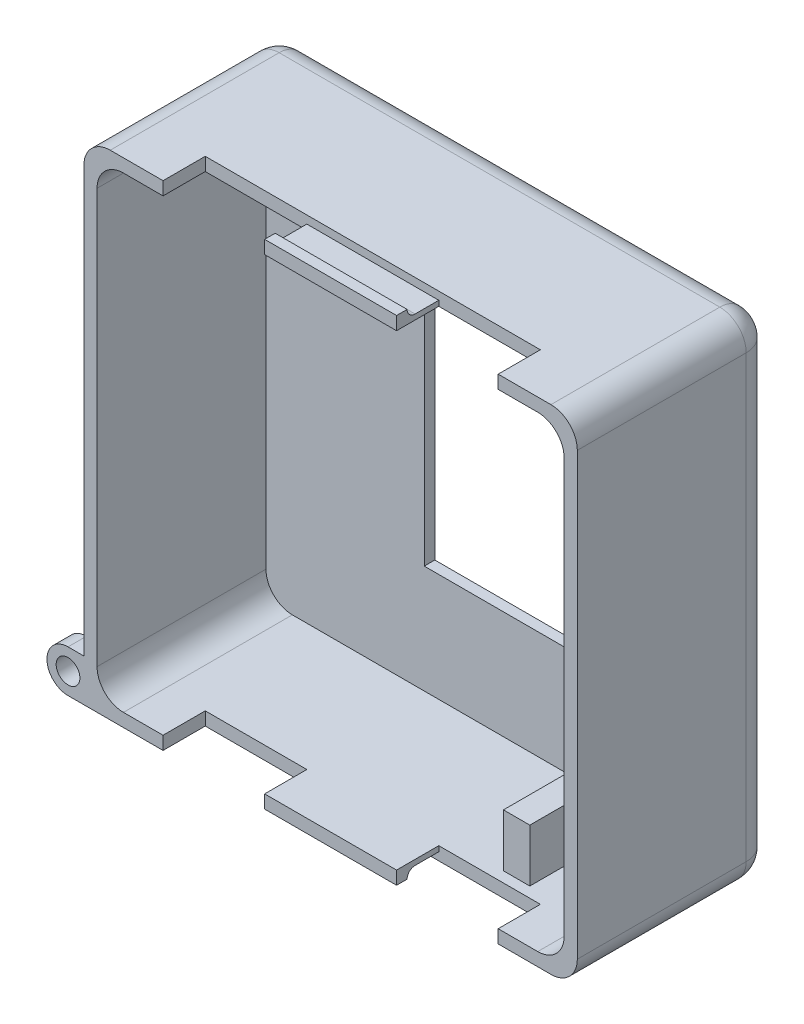
SolidWorks part; units mm, degrees
ref_plane "Front Plane" through (0, 0, 0) normal (0, 0, 1) x (1, 0, 0)
ref_plane "Top Plane" through (0, 0, 0) normal (0, 1, 0) x (1, 0, 0)
ref_plane "Right Plane" through (0, 0, 0) normal (1, 0, 0) x (0, 0, -1)
sketch "Sketch1" plane through (0, 0, 0) normal (0, 0, 1) x (1, 0, 0)
  line L1 (-21.209, -23.749) -> (21.209, -23.749)
  line L2 (-23.749, -21.209) -> (-23.749, 21.209)
  line L3 (-21.209, 23.749) -> (21.209, 23.749)
  line L4 (23.749, -21.209) -> (23.749, 21.209)
  line L5 (-23.749, -23.749) -> (23.749, 23.749) construction
  line L6 (-23.749, 23.749) -> (23.749, -23.749) construction
  arc A0 (-21.209, -23.749) -> (-23.749, -21.209) centre (-21.209, -21.209) cw
  arc A1 (21.209, -23.749) -> (23.749, -21.209) centre (21.209, -21.209) ccw
  arc A2 (21.209, 23.749) -> (23.749, 21.209) centre (21.209, 21.209) cw
  arc A3 (-23.749, 21.209) -> (-21.209, 23.749) centre (-21.209, 21.209) cw
  point P0 (0, 0)
  dimension "D3" = 2.54
  dimension "D1" = 47.498
  dimension "D2" = 47.498
extrude "Boss-Extrude1" add sketch "Sketch1" along normal blind 18.796
sketch "Sketch2" plane through (0, 0, 18.796) normal (0, 0, 1) x (1, 0, 0)
  line L22 (21.209, 23.749) -> (-21.209, 23.749) construction
  line L23 (19.939, -22.479) -> (-19.939, -22.479)
  line L24 (22.479, -19.939) -> (22.479, 19.939)
  line L25 (19.939, 22.479) -> (-19.939, 22.479)
  line L26 (-22.479, -19.939) -> (-22.479, 19.939)
  line L27 (22.479, -22.479) -> (-22.479, 22.479) construction
  line L28 (22.479, 22.479) -> (-22.479, -22.479) construction
  line L29 (-23.749, 21.209) -> (-23.749, -21.209) construction
  arc A14 (-19.939, -22.479) -> (-22.479, -19.939) centre (-19.939, -19.939) cw
  arc A15 (19.939, -22.479) -> (22.479, -19.939) centre (19.939, -19.939) ccw
  arc A16 (22.479, 19.939) -> (19.939, 22.479) centre (19.939, 19.939) ccw
  arc A17 (-19.939, 22.479) -> (-22.479, 19.939) centre (-19.939, 19.939) ccw
  point P12 (0, 0)
  dimension "D3" = 2.54
  dimension "D1" = 1.27
  dimension "D2" = 1.27
extrude "Cut-Extrude1" cut sketch "Sketch2" against normal blind 16.256
fillet "Fillet1" radius 2.54 8 edges at (-23.0051, 23.0051, 0) (0, 23.749, 0) (23.0051, 23.0051, 0) (23.749, 0, 0) (23.0051, -23.0051, 0) (0, -23.749, 0) (-23.0051, -23.0051, 0) (-23.749, 0, 0)
sketch "Sketch3" plane through (0, 23.749, 0) normal (0, 1, 0) x (1, 0, 0)
  line L0 (21.209, -18.796) -> (-21.209, -18.796) construction
  line L1 (16.129, -22.86) -> (-16.129, -22.86)
  line L2 (16.129, -22.86) -> (16.129, -14.732)
  line L3 (16.129, -14.732) -> (-16.129, -14.732)
  line L4 (-16.129, -22.86) -> (-16.129, -14.732)
  line L5 (16.129, -22.86) -> (-16.129, -14.732) construction
  line L6 (16.129, -14.732) -> (-16.129, -22.86) construction
  point P0 (0, -18.796)
  dimension "D1" = 32.258
  dimension "D2" = 4.064
extrude "Cut-Extrude2" cut sketch "Sketch3" against normal through all both and the other way through all
sketch "Sketch5" plane through (0, 0, 0) normal (0, 0, -1) x (-1, 0, 0)
  line L0 (21.209, -21.209) -> (21.209, 21.209) construction
  line L1 (-14.605, 17.145) -> (12.319, 17.145)
  line L2 (-14.605, 17.145) -> (-14.605, -17.145)
  line L3 (-14.605, -17.145) -> (12.319, -17.145)
  line L4 (12.319, 17.145) -> (12.319, -17.145)
  line L5 (-14.605, 17.145) -> (12.319, -17.145) construction
  line L6 (-14.605, -17.145) -> (12.319, 17.145) construction
  point P0 (0, 0)
  dimension "D1" = 26.924
  dimension "D2" = 34.29
  dimension "D3" = 8.89
extrude "Cut-Extrude4" cut sketch "Sketch5" against normal blind 1.524
sketch "Sketch6" plane through (0, 0, 1.524) normal (0, 0, -1) x (-1, 0, 0)
  line L0 (-14.605, 17.145) -> (-14.605, -17.145) construction
  line L1 (-9.525, -12.065) -> (7.239, -12.065)
  line L2 (-9.525, -12.065) -> (-9.525, 12.065)
  line L3 (-9.525, 12.065) -> (7.239, 12.065)
  line L4 (7.239, -12.065) -> (7.239, 12.065)
  line L5 (-9.525, -12.065) -> (7.239, 12.065) construction
  line L6 (-9.525, 12.065) -> (7.239, -12.065) construction
  line L8 (12.319, 17.145) -> (-14.605, 17.145) construction
  line L9 (-14.605, -17.145) -> (12.319, -17.145) construction
  line L10 (12.319, -17.145) -> (12.319, 17.145) construction
  point P0 (0, 0)
  dimension "D1" = 5.08
  dimension "D2" = 5.08
  dimension "D3" = 5.08
  dimension "D4" = 5.08
extrude "Cut-Extrude5" cut sketch "Sketch6" against normal blind 1.524
sketch "Sketch7" plane through (0, 0, 0) normal (0, 0, -1) x (-1, 0, 0)
  line L0 (21.209, 21.209) -> (21.209, -21.209) construction
  line L1 (21.209, 21.209) -> (-21.209, 21.209) construction
  line L2 (-21.209, -21.209) -> (21.209, -21.209) construction
  line L3 (13.589, 21.209) -> (13.589, -21.209) construction
  line L4 (21.209, -21.209) -> (21.209, 21.209) construction
  line L5 (13.589, 17.145) -> (21.209, 17.145) construction
  line L6 (19.939, 17.145) -> (21.209, 17.145)
  line L7 (14.859, 17.145) -> (13.589, 17.145)
  line L8 (21.209, 15.875) -> (16.129, 15.875)
  line L9 (21.209, 10.795) -> (16.129, 10.795)
  line L10 (16.129, 14.605) -> (21.209, 14.605)
  line L11 (21.209, 14.605) -> (21.209, 15.875)
  line L12 (16.129, 12.065) -> (21.209, 12.065)
  line L13 (21.209, 12.065) -> (21.209, 10.795)
  line L14 (13.589, 9.525) -> (21.209, 9.525)
  line L15 (21.209, 9.525) -> (21.209, 5.715)
  line L16 (21.209, 5.715) -> (19.939, 5.715)
  line L17 (19.939, 5.715) -> (19.939, 8.255)
  line L18 (19.939, 8.255) -> (18.034, 8.255)
  line L19 (18.034, 8.255) -> (18.034, 6.985)
  line L20 (18.034, 6.985) -> (16.764, 6.985)
  line L21 (16.764, 6.985) -> (16.764, 8.255)
  line L22 (16.764, 8.255) -> (13.589, 8.255)
  line L23 (13.589, 8.255) -> (13.589, 9.525)
  line L24 (13.589, 4.445) -> (21.209, 4.445)
  line L25 (21.209, 4.445) -> (21.209, 0.635)
  line L26 (21.209, 0.635) -> (19.939, 0.635)
  line L27 (19.939, 0.635) -> (19.939, 3.175)
  line L28 (19.939, 3.175) -> (18.034, 3.175)
  line L29 (18.034, 3.175) -> (18.034, 1.905)
  line L30 (18.034, 1.905) -> (16.764, 1.905)
  line L31 (16.764, 1.905) -> (16.764, 3.175)
  line L32 (16.764, 3.175) -> (13.589, 3.175)
  line L33 (13.589, 3.175) -> (13.589, 4.445)
  line L34 (21.209, -0.635) -> (13.589, -0.635)
  line L35 (13.589, -0.635) -> (13.589, -4.445)
  line L36 (13.589, -4.445) -> (14.859, -4.445)
  line L37 (14.859, -4.445) -> (14.859, -1.905)
  line L38 (14.859, -1.905) -> (21.209, -1.905)
  line L39 (21.209, -1.905) -> (21.209, -0.635)
  line L40 (13.589, -5.715) -> (21.209, -5.715)
  line L41 (21.209, -5.715) -> (21.209, -9.525)
  line L42 (21.209, -9.525) -> (19.939, -9.525)
  line L43 (19.939, -9.525) -> (19.939, -6.985)
  line L44 (19.939, -6.985) -> (18.034, -6.985)
  line L45 (18.034, -6.985) -> (18.034, -8.255)
  line L46 (18.034, -8.255) -> (16.764, -8.255)
  line L47 (16.764, -8.255) -> (16.764, -6.985)
  line L48 (16.764, -6.985) -> (14.859, -6.985)
  line L49 (14.859, -6.985) -> (14.859, -9.525)
  line L50 (14.859, -9.525) -> (13.589, -9.525)
  line L51 (13.589, -9.525) -> (13.589, -5.715)
  line L52 (13.589, -13.0175) -> (21.209, -13.0175) construction
  line L53 (21.209, -13.0175) -> (17.399, -13.0175) construction
  line L54 (17.399, -13.0175) -> (13.589, -13.0175) construction
  line L55 (18.9865, -13.97) -> (18.9865, -15.24)
  line L56 (15.8115, -12.065) -> (15.8115, -10.795)
  line L57 (13.589, -18.7325) -> (21.209, -18.7325) construction
  line L58 (15.8115, -17.78) -> (15.8115, -16.51)
  line L59 (18.9865, -20.955) -> (18.9865, -19.685)
  arc A0 (21.209, 17.145) -> (13.589, 17.145) centre (17.399, 17.145) ccw
  arc A1 (19.939, 17.145) -> (14.859, 17.145) centre (17.399, 17.145) ccw
  arc A2 (16.129, 15.875) -> (16.129, 10.795) centre (16.129, 13.335) ccw
  arc A3 (16.129, 14.605) -> (16.129, 12.065) centre (16.129, 13.335) ccw
  arc A4 (18.9865, -15.24) -> (16.764, -13.0175) centre (18.9865, -13.0175) ccw
  arc A5 (15.8115, -10.795) -> (18.034, -13.0175) centre (15.8115, -13.0175) ccw
  arc A6 (18.9865, -13.97) -> (18.034, -13.0175) centre (18.9865, -13.0175) ccw
  arc A7 (15.8115, -12.065) -> (16.764, -13.0175) centre (15.8115, -13.0175) ccw
  arc A8 (15.8115, -16.51) -> (18.034, -18.7325) centre (15.8115, -18.7325) ccw
  arc A9 (18.9865, -20.955) -> (16.764, -18.7325) centre (18.9865, -18.7325) ccw
  arc A10 (15.8115, -17.78) -> (16.764, -18.7325) centre (15.8115, -18.7325) ccw
  arc A11 (18.9865, -19.685) -> (18.034, -18.7325) centre (18.9865, -18.7325) ccw
  point P15 (13.589, 0)
  dimension "D3" = 5.08
  dimension "D4" = 17.145
  dimension "D5" = 2.54
  dimension "D6" = 5.08
  dimension "D40" = 4.445
  dimension "D41" = 1.27
  dimension "D42" = 1.905
  dimension "D43" = 4.445
  dimension "D44" = 1.27
  dimension "D46" = 1.905
  dimension "D1" = 7.62
  dimension "D2" = 0
  dimension "D7" = 1.27
  dimension "D8" = 1.27
  dimension "D9" = 1.27
  dimension "D10" = 1.27
  dimension "D11" = 1.27
  dimension "D12" = 1.27
  dimension "D13" = 1.905
  dimension "D14" = 1.27
  dimension "D15" = 2.54
  dimension "D16" = 3.81
  dimension "D17" = 1.27
  dimension "D18" = 1.27
  dimension "D19" = 1.27
  dimension "D20" = 1.27
  dimension "D21" = 1.905
  dimension "D22" = 1.27
  dimension "D23" = 2.54
  dimension "D24" = 3.81
  dimension "D25" = 1.27
  dimension "D26" = 1.27
  dimension "D27" = 1.27
  dimension "D28" = 3.81
  dimension "D29" = 1.27
  dimension "D30" = 1.27
  dimension "D31" = 1.27
  dimension "D32" = 1.27
  dimension "D33" = 1.27
  dimension "D34" = 2.54
  dimension "D35" = 2.54
  dimension "D36" = 3.81
  dimension "D37" = 3.81
  dimension "D38" = 1.905
  dimension "D39" = 1.27
sketch "Sketch8" plane through (0, 0, 14.732) normal (0, 0, 1) x (1, 0, 0)
  line L0 (16.129, 22.479) -> (-16.129, 22.479) construction
  line L1 (6.35, 22.987) -> (-6.35, 22.987)
  line L2 (6.35, 22.987) -> (6.35, 22.479)
  line L3 (6.35, 22.479) -> (-6.35, 22.479)
  line L4 (-6.35, 22.987) -> (-6.35, 22.479)
  line L5 (6.35, 22.987) -> (-6.35, 22.479) construction
  line L6 (6.35, 22.479) -> (-6.35, 22.987) construction
  line L7 (-16.129, -22.479) -> (16.129, -22.479) construction
  line L8 (6.35, -22.987) -> (-6.35, -22.987)
  line L9 (6.35, -22.987) -> (6.35, -22.479)
  line L10 (6.35, -22.479) -> (-6.35, -22.479)
  line L11 (-6.35, -22.987) -> (-6.35, -22.479)
  line L12 (6.35, -22.987) -> (-6.35, -22.479) construction
  line L13 (6.35, -22.479) -> (-6.35, -22.987) construction
  point P0 (0, 22.733)
  point P7 (0, -22.733)
  dimension "D1" = 0.508
  dimension "D2" = 12.7
  dimension "D3" = 0
  dimension "D4" = 0.508
  dimension "D5" = 12.7
  dimension "D6" = 0
extrude "Boss-Extrude3" add sketch "Sketch8" along normal blind 4.064
sketch "Sketch9" plane through (0, 22.987, 0) normal (0, 1, 0) x (1, 0, 0)
  line L1 (6.35, -18.796) -> (6.35, -14.732) construction
  line L2 (-6.35, -18.796) -> (6.35, -18.796)
  line L3 (-6.35, -18.796) -> (-6.35, -17.78)
  line L4 (-6.35, -17.78) -> (6.35, -17.78)
  line L5 (6.35, -18.796) -> (6.35, -17.78)
  dimension "D1" = 1.016
extrude "Boss-Extrude4" add sketch "Sketch9" along normal blind 0.762
fillet "Fillet2" radius 0.762 1 edges at (0, 22.987, 17.78)
sketch "Sketch10" plane through (0, -22.987, 0) normal (0, -1, 0) x (1, 0, 0)
  line L0 (-6.35, 18.796) -> (-6.35, 14.732) construction
  line L1 (6.35, 18.796) -> (-6.35, 18.796)
  line L2 (6.35, 18.796) -> (6.35, 17.78)
  line L3 (6.35, 17.78) -> (-6.35, 17.78)
  line L4 (-6.35, 18.796) -> (-6.35, 17.78)
  dimension "D1" = 1.016
extrude "Boss-Extrude5" add sketch "Sketch10" along normal blind 0.762
fillet "Fillet3" radius 0.762 1 edges at (0, -22.987, 17.78)
sketch "Sketch11" plane through (-23.749, 0, 0) normal (-1, 0, 0) x (0, 0, 1)
  line L1 (18.796, -23.749) -> (17.018, -23.749)
  line L2 (18.796, -23.749) -> (18.796, -19.685)
  line L3 (18.796, -19.685) -> (17.018, -19.685)
  line L4 (17.018, -23.749) -> (17.018, -19.685)
  dimension "D1" = 4.064
  dimension "D2" = 1.778
extrude "Boss-Extrude6" add sketch "Sketch11" along normal blind 3.556 and the other way up to body separate body
fillet "Fillet4" 2 edges at (-27.305, -19.685, 17.907) (-27.305, -23.749, 17.907) type full round first side face at (-25.527, -19.685, 17.907) second side face at (-5.461, -23.749, 14.3764) middle face at (-27.305, -21.717, 17.907)
sketch "Sketch12" plane through (0, 0, 17.018) normal (0, 0, -1) x (-1, 0, 0)
  circle A0 centre (25.273, -21.717) radius 1.143
  dimension "D1" = 2.286
extrude "Cut-Extrude7" cut sketch "Sketch12" against normal blind 4.064
extrude "Cut-Extrude8" cut sketch "Sketch7" against normal blind 0.762
sketch "Sketch13" plane through (0, 0, 2.54) normal (0, 0, 1) x (1, 0, 0)
  line L0 (-19.939, -22.479) -> (19.939, -22.479) construction
  line L1 (19.177, -12.319) -> (16.637, -12.319)
  line L2 (19.177, -12.319) -> (19.177, -17.399)
  line L3 (19.177, -17.399) -> (16.637, -17.399)
  line L4 (16.637, -12.319) -> (16.637, -17.399)
  line L5 (19.177, -12.319) -> (16.637, -17.399) construction
  line L6 (19.177, -17.399) -> (16.637, -12.319) construction
  line L7 (22.479, -19.939) -> (22.479, 19.939) construction
  point P1 (17.907, -14.859)
  dimension "D1" = 7.62
  dimension "D2" = 3.302
  dimension "D3" = 2.54
  dimension "D4" = 5.08
extrude "Boss-Extrude7" add sketch "Sketch13" along normal blind 16.256
sketch "Sketch15" plane through (19.177, 0, 0) normal (1, 0, 0) x (0, 0, -1)
  line L0 (-18.796, -17.399) -> (-18.796, -12.319) construction
  line L1 (-13.716, -16.129) -> (-2.54, -16.129)
  line L2 (-13.716, -16.129) -> (-13.716, -13.589)
  line L3 (-13.716, -13.589) -> (-2.54, -13.589)
  line L4 (-2.54, -16.129) -> (-2.54, -13.589)
  point P6 (-13.716, -14.859)
  point P7 (-18.796, -14.859)
  dimension "D1" = 5.08
  dimension "D2" = 11.176
  dimension "D3" = 2.54
  dimension "D4" = 0
extrude "Boss-Extrude8" add sketch "Sketch15" along normal blind 3.556
